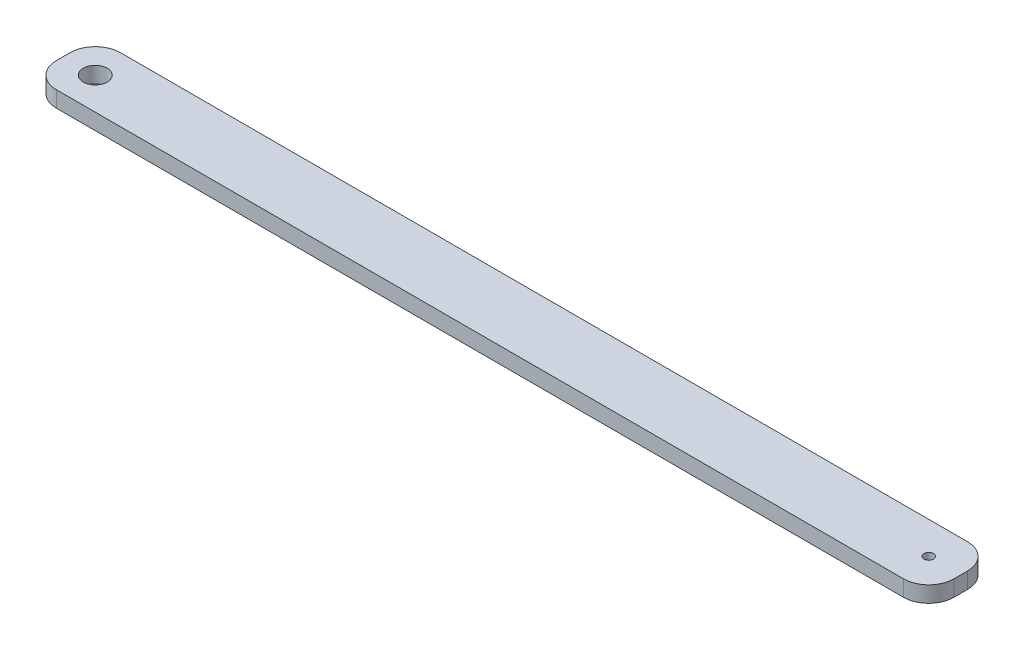
SolidWorks part; units mm, degrees
material "5052-O"
ref_plane "Front Plane" through (0, 0, 0) normal (0, 0, 1) x (1, 0, 0)
ref_plane "Top Plane" through (0, 0, 0) normal (0, 1, 0) x (1, 0, 0)
ref_plane "Right Plane" through (0, 0, 0) normal (1, 0, 0) x (0, 0, -1)
sketch "Sketch1" plane through (0, 0, 0) normal (0, 1, 0) x (1, 0, 0)
  line L1 (-177.8, -12.7) -> (177.8, -12.7)
  line L2 (-177.8, -12.7) -> (-177.8, 12.7)
  line L3 (-177.8, 12.7) -> (177.8, 12.7)
  line L4 (177.8, -12.7) -> (177.8, 12.7)
  line L5 (-177.8, -12.7) -> (177.8, 12.7) construction
  line L6 (-177.8, 12.7) -> (177.8, -12.7) construction
  point P0 (0, 0)
  dimension "D1" = 25.4
  dimension "D2" = 355.6
extrude "Boss-Extrude1" add sketch "Sketch1" along normal mid plane 6.35
fillet "Fillet1" radius 10 4 edges at (177.8, 0, -12.7) (177.8, 0, 12.7) (-177.8, 0, -12.7) (-177.8, 0, 12.7)
sketch "Sketch2" plane through (0, 3.175, 0) normal (0, 1, 0) x (1, 0, 0)
  line L0 (0, -36.7292) -> (0, 36.7292) construction
  line L1 (165.1, 0) -> (-165.1, 0) construction
  line L2 (-177.8, 2.7) -> (-177.8, -2.7) construction
  point P10 (0, 0)
  point P11 (0, 0)
  dimension "D1" = 12.7
hole_wizard "#10-24 Tapped Hole1" positions "Sketch5" profile "Sketch7" tap size "#10-24" standard "ANSI Inch" end condition through all
sketch "Sketch5" plane through (0, 3.175, 0) normal (0, 1, 0) x (1, 0, 0)
  point P0 (165.1, 0)
sketch "Sketch7" plane through (165.1, 3.175, 0) normal (1, 0, 0) x (0, 0, 1)
  line L0 (0, 0) -> (0, 6.35)
  line L1 (0, 6.35) -> (1.8986, 6.35)
  line L2 (1.8986, 6.35) -> (1.8986, 0)
  line L5 (1.8986, 0) -> (0, 0)
  line L11 (0, -6.35) -> (0, 107.95) construction
  dimension "Thru Tap Drill Dia." = 3.7973
  dimension "Thru Tap Drill Depth" = 6.35
cosmetic thread "Hole Thread1" parameters "D2"=4.826
sketch "Sketch8" plane through (0, 3.175, 0) normal (0, 1, 0) x (1, 0, 0)
  circle A0 centre (-165.1, 0) radius 4.7625
  dimension "D1" = 9.525
extrude "Cut-Extrude1" cut sketch "Sketch8" against normal through all
sketch "Sketch9" plane through (0, 3.175, 0) normal (0, 1, 0) x (1, 0, 0)
  line L0 (-177.8, 2.7) -> (-177.8, -2.7) construction
  line L1 (-142.875, -6.35) -> (-136.525, -6.35)
  line L2 (-142.875, -6.35) -> (-142.875, -9.525)
  line L3 (-142.875, -9.525) -> (-136.525, -9.525)
  line L4 (-136.525, -6.35) -> (-136.525, -9.525)
  line L5 (-142.875, -6.35) -> (-136.525, -9.525) construction
  line L6 (-142.875, -9.525) -> (-136.525, -6.35) construction
  line L7 (-167.8, -12.7) -> (167.8, -12.7) construction
  point P4 (-139.7, -7.9375)
  dimension "D1" = 3.175
  dimension "D2" = 6.35
  dimension "D3" = 38.1
  dimension "D4" = 3.175
extrude "Cut-Extrude2" [suppressed] cut sketch "Sketch9" against normal through all
fillet "Fillet2" [suppressed] radius 0.635
pattern_linear "LPattern1" [suppressed] count 3 spacing 69.85 of bodies 105
mirror "Mirror1" [suppressed] about plane through (0, 0, 0) normal (1, 0, 0)
